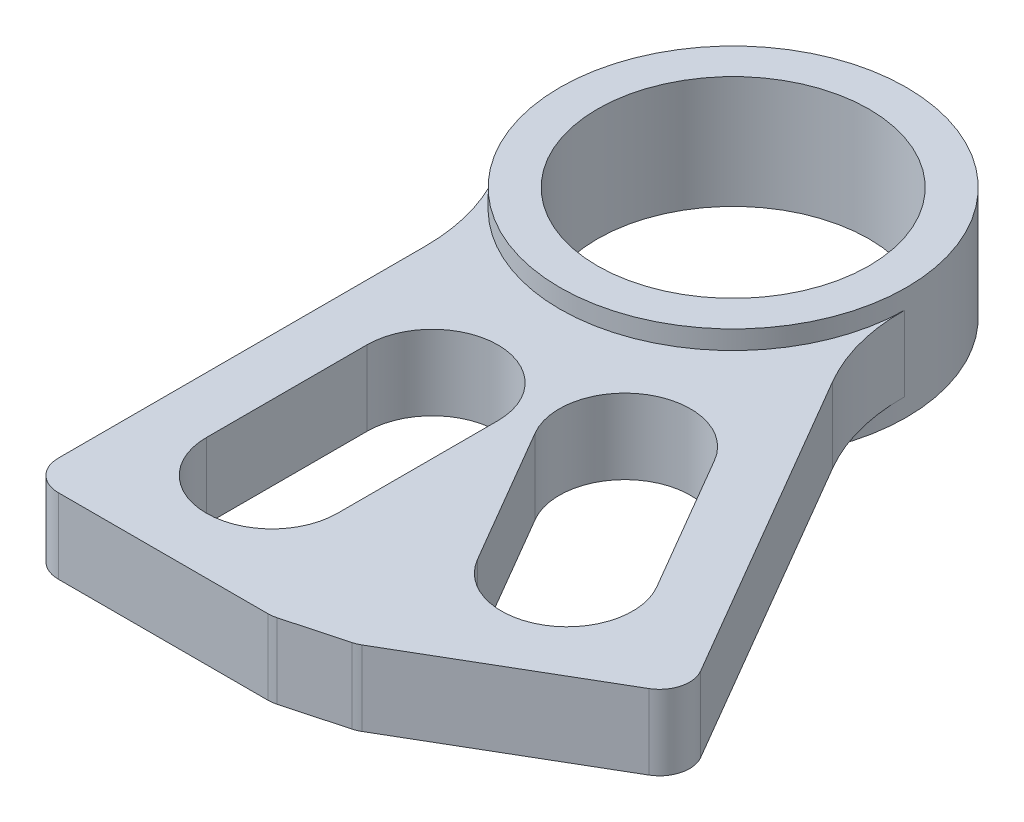
SolidWorks part; units mm, degrees
ref_plane "Front Plane" through (0, 0, 0) normal (0, 0, 1) x (1, 0, 0)
ref_plane "Top Plane" through (0, 0, 0) normal (0, 1, 0) x (1, 0, 0)
ref_plane "Right Plane" through (0, 0, 0) normal (1, 0, 0) x (0, 0, -1)
sketch "Sketch1" plane through (0, 0, 0) normal (0, 1, 0) x (1, 0, 0)
  line L0 (0, 0) -> (0, -49.3903) construction
  line L1 (0, 0) -> (24.8801, -42.666) construction
  line L2 (0, -39.0716) -> (0, -25.4826) construction
  line L3 (-5.5562, -39.0716) -> (-5.5562, -25.4826)
  line L4 (5.5563, -39.0716) -> (5.5563, -25.4826)
  line L5 (19.6821, -33.7521) -> (12.8367, -22.0132) construction
  line L6 (14.8823, -36.551) -> (8.0369, -24.8121)
  line L7 (24.4818, -30.9531) -> (17.6365, -19.2142)
  line L8 (0, -49.3903) -> (0, -44.6278) construction
  line L9 (24.8801, -42.666) -> (22.481, -38.5519) construction
  line L10 (-10.3187, -49.3903) -> (10.3188, -49.3903)
  line L11 (15.9662, -47.864) -> (33.794, -37.4679)
  line L12 (-10.3187, -49.3903) -> (-10.3187, -10.4432)
  line L13 (10.3188, -49.3903) -> (10.3188, -38.1794)
  line L14 (33.794, -37.4679) -> (14.1746, -3.8234)
  line L15 (15.9662, -47.864) -> (10.3188, -38.1794)
  line L16 (181.7674, -311.7065) -> (14.7943, -25.3703) construction
  line L17 (10.3188, -49.3903) -> (15.9662, -47.864)
  line L22 (0, 0) -> (10.3188, -38.1794) construction
  circle A0 centre (0, 0) radius 11.5062
  circle A1 centre (0, 0) radius 14.6812
  arc A2 (-5.5562, -39.0716) -> (5.5563, -39.0716) centre (0, -39.0716) ccw
  arc A3 (5.5563, -25.4826) -> (-5.5562, -25.4826) centre (0, -25.4826) ccw
  arc A4 (14.8823, -36.551) -> (24.4818, -30.9531) centre (19.6821, -33.7521) ccw
  arc A5 (17.6365, -19.2142) -> (8.0369, -24.8121) centre (12.8367, -22.0132) ccw
  point P8 (0, -32.2771)
  point P13 (16.2594, -27.8826)
  point P25 (0, -49.3903)
  point P27 (24.8801, -42.666)
  dimension "D2" = 29.3624
  dimension "D3" = 4.7625
  dimension "D4" = 4.7625
  dimension "D5" = 13.589
  dimension "D6" = 49.3903
  dimension "D7" = 20.6375
extrude "Bearing_Insert_Extrude" add sketch "Sketch1" along normal mid plane 9.525 contours A1 A0 region at (-5.4988, 0, -13.1636)
extrude "Apex_Slot_Insert_Extrude" add sketch "Sketch1<4>" along normal mid plane 6.35 contours A1 L12 L10 L13 L15 L11 L14 A5 L7 A4 L6 A3 L4 A2 L3 | L13 L17 L15 region at (8.1875, 0, 30.2936) region at (12.2012, 0, 45.1445)
sketch "Sketch1<4>" plane through (0, 0, 0) normal (0, 1, 0) x (1, 0, 0) same geometry as "Sketch1"
fillet "Fillet1" radius 16.002 2 edges at (14.1746, 0, 3.8234) (-10.3187, 0, 10.4432)
fillet "Fillet2" radius 2.54 4 edges at (33.794, 0, 37.4679) (-10.3187, 0, 49.3903) (15.9662, 0, 47.864) (10.3188, 0, 49.3903)
equation "\"Apex_thickness\"= .25"
equation "\"Bearing_diameter\"= 0.906in"
equation "\"A-arm_angle\"= 39.1893"
equation "\"D1@Sketch1\"=\"Bearing_diameter\""
equation "\"D1@Apex_Slot_Insert_Extrude\"=\"Apex_thickness\""
